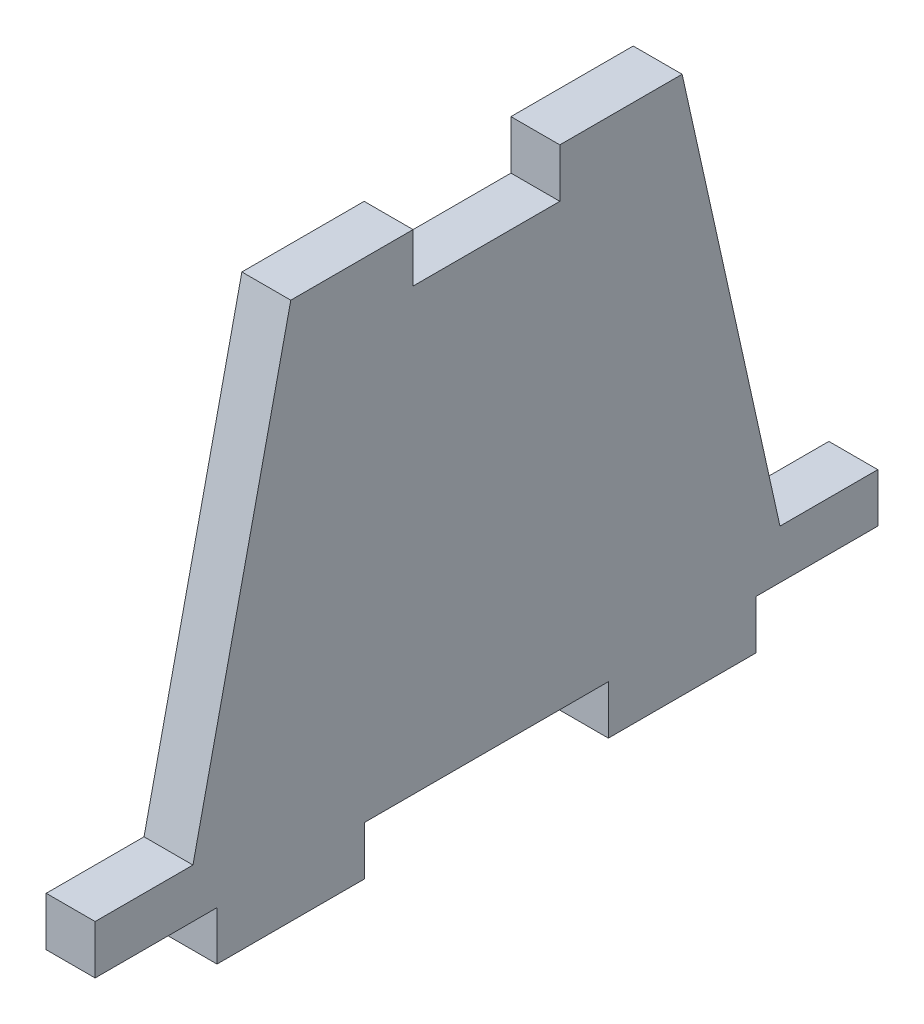
SolidWorks part; units mm, degrees
ref_plane "Front Plane" through (0, 0, 0) normal (0, 0, 1) x (1, 0, 0)
ref_plane "Top Plane" through (0, 0, 0) normal (0, 1, 0) x (1, 0, 0)
ref_plane "Right Plane" through (0, 0, 0) normal (1, 0, 0) x (0, 0, -1)
sketch "Sketch1" plane through (0, 0, 0) normal (1, 0, 0) x (0, 0, -1)
  line L0 (-25.4, 0) -> (-17.4879, 0)
  line L1 (25.4, 0) -> (25.4, 3.175)
  line L2 (25.4, 3.175) -> (19.05, 3.175)
  line L3 (19.05, 3.175) -> (12.7, 31.75)
  line L6 (12.7, 31.75) -> (4.7625, 31.75)
  line L7 (-12.7, 31.75) -> (-19.05, 3.175)
  line L8 (-19.05, 3.175) -> (-25.4, 3.175)
  line L9 (-25.4, 3.175) -> (-25.4, 0)
  line L10 (-4.7625, 31.75) -> (-12.7, 31.75)
  line L11 (-4.7625, 28.575) -> (4.7625, 28.575)
  line L12 (-4.7625, 28.575) -> (-4.7625, 31.75)
  line L14 (4.7625, 28.575) -> (4.7625, 31.75)
  line L15 (-17.4879, 0) -> (-17.4879, -3.175)
  line L16 (-17.4879, -3.175) -> (-7.9121, -3.175)
  line L17 (-7.9121, -3.175) -> (-7.9121, 0)
  line L18 (7.9121, 0) -> (7.9121, -3.175)
  line L19 (7.9121, -3.175) -> (17.4879, -3.175)
  line L20 (17.4879, -3.175) -> (17.4879, 0)
  line L21 (-7.9121, 0) -> (7.9121, 0)
  line L22 (17.4879, 0) -> (25.4, 0)
  point P0 (0, 28.575)
  point P4 (0, 0)
  point P24 (-12.7, -3.175)
  dimension "D1" = 31.75
  dimension "D2" = 3.175
  dimension "D3" = 50.8
  dimension "D4" = 25.4
  dimension "D5" = 6.35
  dimension "D6" = 9.525
  dimension "D7" = 3.175
  dimension "D8" = 9.5758
  dimension "D9" = 3.175
  dimension "D10" = 9.5758
  dimension "D11" = 12.7
extrude "Boss-Extrude1" add sketch "Sketch1" along normal mid plane 3.175 contours L7 L8 L9 L0 L15 L16 L17 L21 L18 L19 L20 L22 L1 L2 L3 L6 L14 L11 L12 L10
equation "\"D8@Sketch1\"=0.375+0.002"
